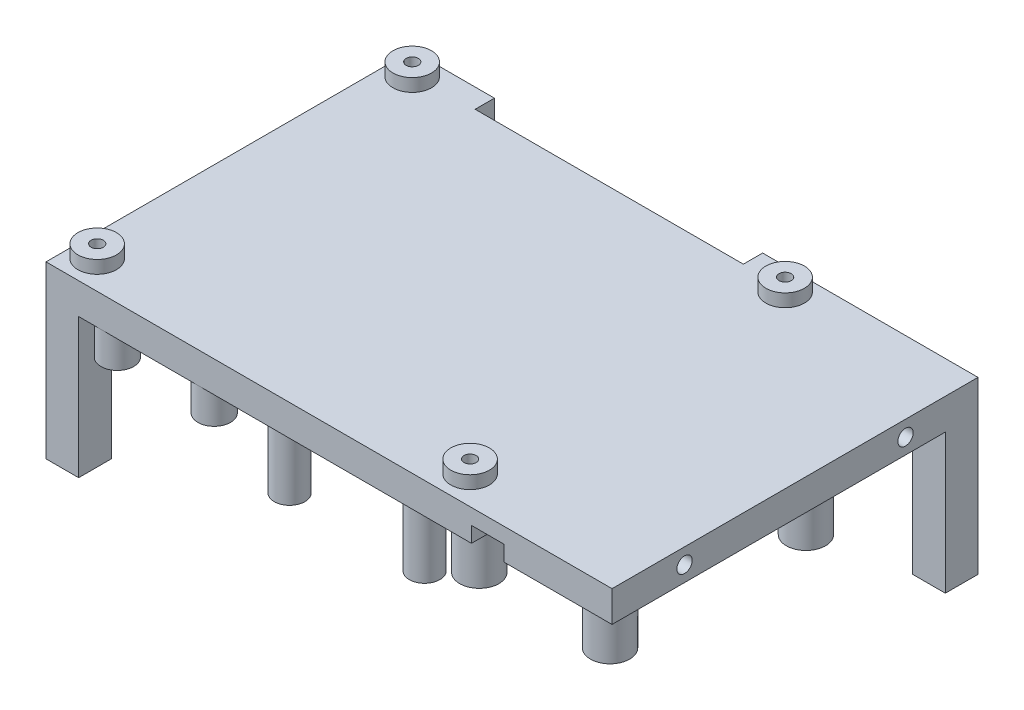
SolidWorks part; units mm, degrees
ref_plane "Front Plane" through (0, 0, 0) normal (0, 0, 1) x (1, 0, 0)
ref_plane "Top Plane" through (0, 0, 0) normal (0, 1, 0) x (1, 0, 0)
ref_plane "Right Plane" through (0, 0, 0) normal (1, 0, 0) x (0, 0, -1)
sketch "Sketch2" plane through (0, 0, 0) normal (0, 1, 0) x (1, 0, 0)
  line L1 (0, 0) -> (83.674, 0)
  line L2 (0, 0) -> (0, 58.032)
  line L3 (0, 58.032) -> (83.674, 58.032)
  line L4 (83.674, 0) -> (83.674, 58.032)
extrude "Boss-Extrude1" add sketch "Sketch2" along normal blind 2.54
sketch "Sketch4" plane through (0, 2.54, 0) normal (0, 1, 0) x (1, 0, 0)
  line L0 (88.037, 54.5711) -> (88.037, 58.032)
  line L1 (87.642, 54.5711) -> (88.432, 54.5711) construction
  line L2 (88.037, 58.032) -> (83.674, 58.032)
  line L3 (83.674, 58.032) -> (83.674, 0)
  line L4 (83.674, 0) -> (87.642, 0)
  line L5 (88.037, 54.5711) -> (88.037, 0)
  line L6 (88.037, 0) -> (87.642, 0)
extrude "Boss-Extrude2" add sketch "Sketch4" against normal blind 2.54
sketch "Sketch5" plane through (0, 2.54, 0) normal (0, 1, 0) x (1, 0, 0)
  line L0 (3.042, 56.9211) -> (0, 56.9211) construction
  line L1 (0, 58.032) -> (0, 0) construction
  line L3 (0, 56.9211) -> (88.037, 56.9211)
  line L4 (0, 56.9211) -> (0, 58.032)
  line L5 (0, 58.032) -> (88.037, 58.032)
  line L6 (88.037, 56.9211) -> (88.037, 58.032)
extrude "Cut-Extrude1" cut sketch "Sketch5" against normal blind 2.54
sketch "Sketch6" plane through (0, 2.54, 0) normal (0, 1, 0) x (1, 0, 0)
  circle A0 centre (3.542, 53.4211) radius 1.3
  circle A1 centre (3.542, 53.4211) radius 3
  circle A2 centre (61.542, 53.4211) radius 1.35
  circle A3 centre (61.542, 53.4211) radius 3
  circle A4 centre (61.542, 4.4211) radius 1.35
  circle A5 centre (61.542, 4.4211) radius 3
  circle A6 centre (3.542, 4.4211) radius 1.35
  circle A7 centre (3.542, 4.4211) radius 3
extrude "Boss-Extrude3" add sketch "Sketch6" along normal blind 3.81
sketch "Sketch7" plane through (0, 0, 0) normal (0, -1, 0) x (1, 0, 0)
  circle A0 centre (27.0717, -5.4061) radius 1.25
  circle A1 centre (27.0717, -5.4061) radius 2.55
  circle A2 centre (27.0717, -18.1061) radius 1.25
  circle A3 centre (27.0717, -18.1061) radius 2.55
  circle A4 centre (26.076, -32.9835) radius 1.4324
  circle A5 centre (26.076, -32.9835) radius 2.5467
  circle A6 centre (26.0531, -48.0443) radius 1.5084
  circle A7 centre (26.0531, -48.0443) radius 2.659
  circle A8 centre (34.2431, -29.5473) radius 1.1
  circle A9 centre (34.2431, -29.5473) radius 2.375
  circle A10 centre (55.2431, -29.5473) radius 1.1
  circle A11 centre (55.2431, -29.5473) radius 2.375
  circle A12 centre (55.2431, -42.0473) radius 1.1
  circle A13 centre (55.2431, -42.0473) radius 2.375
  circle A14 centre (34.2431, -42.0473) radius 1.1
  circle A15 centre (34.2431, -42.0473) radius 2.375
  circle A16 centre (61.9524, -36.3134) radius 1.6
  circle A17 centre (61.9524, -36.3134) radius 2.5
  circle A18 centre (82.2924, -36.3134) radius 1.6
  circle A19 centre (82.2924, -36.3134) radius 2.5
  circle A20 centre (61.9916, -5.8135) radius 1.6
  circle A21 centre (61.9916, -5.8135) radius 2.6109
  circle A22 centre (82.3316, -5.8135) radius 1.6
  circle A23 centre (82.3316, -5.8135) radius 2.6
extrude "Boss-Extrude4" add sketch "Sketch7" along normal blind 5.08
sketch "Sketch12" plane through (0, 2.54, 0) normal (0, 1, 0) x (1, 0, 0)
  line L0 (3.542, 54.7211) -> (2.242, 54.7211) construction
  line L1 (2.242, 54.7211) -> (2.242, 53.4211) construction
  line L2 (61.542, 3.0711) -> (79.322, 3.0711) construction
  line L4 (79.322, 3.0711) -> (2.242, 3.0711)
  line L5 (79.322, 3.0711) -> (79.322, 54.7211)
  line L6 (79.322, 54.7211) -> (2.242, 54.7211)
  line L7 (2.242, 3.0711) -> (2.242, 54.7211)
  line L8 (0, 56.9211) -> (88.037, 56.9211)
  line L9 (0, 56.9211) -> (0, 0)
  line L10 (0, 0) -> (88.037, 0)
  line L11 (88.037, 56.9211) -> (88.037, 0)
  circle A0 centre (3.542, 53.4211) radius 1.3 construction
  circle A1 centre (61.542, 4.4211) radius 1.35 construction
extrude "Boss-Extrude5" add sketch "Sketch12" along normal blind 2.286
sketch "Sketch13" plane through (0, 0, 0) normal (0, 0, 1) x (1, 0, 0)
  line L0 (0, 2.413) -> (5.08, 2.413) construction
  line L1 (0, 4.826) -> (0, 0) construction
  line L2 (88.037, 2.413) -> (82.957, 2.413) construction
  line L3 (88.037, 0) -> (88.037, 4.826) construction
  circle A0 centre (82.957, 2.413) radius 1.27
  circle A1 centre (5.08, 2.413) radius 1.27
extrude "Boss-Extrude6" add sketch "Sketch13" along normal blind 10.16
sketch "Sketch14" plane through (0, 0, 0) normal (0, 0, 1) x (1, 0, 0)
  circle A0 centre (5.08, 2.413) radius 1.27
  circle A1 centre (82.957, 2.413) radius 1.27
extrude "Boss-Extrude7" add sketch "Sketch14" against normal blind 10.16 from surface starting at face at (44.0185, 2.413, -56.9211)
sketch "Sketch15" plane through (0, 0, 10.16) normal (0, 0, 1) x (1, 0, 0)
  circle A0 centre (5.08, 2.413) radius 1.27
  circle A1 centre (82.957, 2.413) radius 1.27
extrude "Cut-Extrude3" cut sketch "Sketch15" against normal blind 12.7
sketch "Sketch16" plane through (0, 0, -67.0811) normal (0, 0, -1) x (-1, 0, 0)
  line L0 (-81.687, 2.413) -> (-76.607, 2.413) construction
  line L1 (-6.35, 2.413) -> (-11.43, 2.413) construction
  circle A0 centre (-82.957, 2.413) radius 1.27 construction
  circle A1 centre (-5.08, 2.413) radius 1.27 construction
  circle A2 centre (-76.607, 2.413) radius 1.27
  circle A3 centre (-11.43, 2.413) radius 1.27
extrude "Boss-Extrude8" add sketch "Sketch16" against normal blind 12.7
sketch "Sketch17" plane through (0, 0, -67.0811) normal (0, 0, -1) x (-1, 0, 0)
  circle A0 centre (-82.957, 2.413) radius 1.27
  circle A1 centre (-5.08, 2.413) radius 1.27
extrude "Cut-Extrude4" cut sketch "Sketch17" against normal up to surface (10.16 mm away) up to face at (12.7, 2.413, -56.9211)
sketch "Sketch18" plane through (0, 0, -67.0811) normal (0, 0, -1) x (-1, 0, 0)
  circle A0 centre (-76.607, 2.413) radius 1.27
  circle A1 centre (-11.43, 2.413) radius 1.27
extrude "Cut-Extrude5" cut sketch "Sketch18" against normal blind 15.24 and the other way through all
sketch "Sketch19" plane through (0, 0, 0) normal (0, -1, 0) x (1, 0, 0)
  line L1 (0, 0) -> (88.037, 0)
  line L2 (0, 0) -> (0, -56.9211)
  line L3 (0, -56.9211) -> (88.037, -56.9211)
  line L4 (88.037, 0) -> (88.037, -56.9211)
extrude "Boss-Extrude9" add sketch "Sketch19" against normal up to surface (4.826 mm away) up to face at (41.6109, 4.826, -28.9106)
sketch "Sketch20" plane through (0, 0, 0) normal (0, 0, 1) x (1, 0, 0)
  line L0 (6.542, 5) -> (6.542, 0) construction
  line L1 (6.542, 4.826) -> (6.542, 6.35) construction
  line L2 (12.722, 5) -> (1.642, 5) construction
  line L3 (0, 0) -> (88.037, 0) construction
  line L4 (6.542, 2.5) -> (9.082, 2.5) construction
  line L5 (79.7316, -0.6431) -> (79.7316, 4.1697) construction
  line L6 (79.7316, 0) -> (79.7316, -5.08) construction
  line L7 (79.7316, -0.6431) -> (79.7316, 4.826) construction
  line L8 (0, 4.826) -> (88.037, 4.826) construction
  line L9 (88.037, 2.413) -> (79.7316, 2.413) construction
  line L10 (88.037, 0) -> (88.037, 4.826) construction
  line L11 (79.7316, 2.413) -> (77.1916, 2.413) construction
  circle A0 centre (9.082, 2.5) radius 1.27
  circle A1 centre (77.1916, 2.413) radius 1.27
extrude "Cut-Extrude6" cut sketch "Sketch20" against normal blind 60.96
sketch "Sketch21" plane through (0, 0, -56.9211) normal (0, 0, -1) x (-1, 0, 0)
  circle A0 centre (-77.1916, 2.413) radius 1.27
  circle A1 centre (-9.082, 2.5) radius 1.27
extrude "Boss-Extrude10" add sketch "Sketch21" against normal blind 49.53 from offset 3.81 offset against normal yes
sketch "Sketch22" plane through (0, 0, 0) normal (0, -1, 0) x (1, 0, 0)
  line L0 (0, 0) -> (2.54, 0) construction
  line L1 (0, 0) -> (88.037, 0) construction
  line L2 (2.54, 0) -> (2.54, -2.54) construction
  line L3 (88.037, -56.9211) -> (85.497, -56.9211) construction
  line L4 (0, -56.9211) -> (88.037, -56.9211) construction
  line L5 (85.497, -56.9211) -> (85.497, -54.3811) construction
  line L6 (2.54, -2.54) -> (5.08, -2.54) construction
  line L7 (5.08, -2.54) -> (5.08, -5.08) construction
  line L8 (85.497, -54.3811) -> (82.957, -54.3811) construction
  line L9 (5.08, -5.08) -> (0, -5.08)
  line L10 (5.08, -5.08) -> (5.08, 0)
  line L11 (5.08, 0) -> (0, 0)
  line L12 (0, -5.08) -> (0, 0)
  line L13 (82.957, -54.3811) -> (82.957, -51.8411) construction
  line L14 (0, -28.4606) -> (14.3355, -28.4606) construction
  line L15 (82.957, -51.8411) -> (88.037, -51.8411)
  line L16 (82.957, -51.8411) -> (82.957, -56.9211)
  line L17 (82.957, -56.9211) -> (88.037, -56.9211)
  line L18 (88.037, -51.8411) -> (88.037, -56.9211)
  line L19 (0, -56.9211) -> (0, 0) construction
  line L20 (5.08, -56.9211) -> (0, -56.9211)
  line L21 (0, -51.8411) -> (0, -56.9211)
  line L22 (5.08, -51.8411) -> (0, -51.8411)
  line L23 (5.08, -51.8411) -> (5.08, -56.9211)
  circle A1 centre (2.54, -2.54) radius 1.27
  circle A2 centre (85.497, -54.3811) radius 1.27
  circle A3 centre (2.54, -54.3811) radius 1.27
extrude "Boss-Extrude11" add sketch "Sketch22" along normal blind 5.08 contours L20 L21 L22 L23 | A3 | L10 L9 L12 L11 | A1 | L16 L15 L18 L17 | A2
sketch "Sketch23" plane through (0, -5.08, 0) normal (0, -1, 0) x (1, 0, 0)
  line L1 (88.037, -56.9211) -> (82.957, -56.9211)
  line L2 (88.037, -56.9211) -> (88.037, -51.8411)
  line L3 (88.037, -51.8411) -> (82.957, -51.8411)
  line L4 (82.957, -56.9211) -> (82.957, -51.8411)
  line L5 (0, -56.9211) -> (5.08, -56.9211)
  line L6 (0, -56.9211) -> (0, -51.8411)
  line L7 (0, -51.8411) -> (5.08, -51.8411)
  line L8 (5.08, -56.9211) -> (5.08, -51.8411)
  line L9 (0, 0) -> (5.08, 0)
  line L10 (0, 0) -> (0, -5.08)
  line L11 (0, -5.08) -> (5.08, -5.08)
  line L12 (5.08, 0) -> (5.08, -5.08)
  circle A0 centre (2.54, -2.54) radius 1.27
  circle A1 centre (2.54, -54.3811) radius 1.27
  circle A2 centre (85.497, -54.3811) radius 1.27
extrude "Boss-Extrude12" add sketch "Sketch23" along normal blind 5.08
sketch "Sketch24" plane through (0, 0, 0) normal (0, -1, 0) x (1, 0, 0)
  line L1 (58.0196, -2.0522) -> (87.0405, -2.0522)
  line L2 (58.0196, -2.0522) -> (58.0196, -39.3757)
  line L3 (58.0196, -39.3757) -> (87.0405, -39.3757)
  line L4 (87.0405, -2.0522) -> (87.0405, -39.3757)
extrude "Cut-Extrude7" cut sketch "Sketch24" along normal blind 7.62
sketch "Sketch25" plane through (0, 0, 0) normal (0, -1, 0) x (1, 0, 0)
  circle A0 centre (64.5432, -22.4957) radius 2.5083
  circle A1 centre (64.5432, -22.4957) radius 3.5101
  circle A2 centre (80.977, -22.4957) radius 2.5082
  circle A3 centre (80.977, -22.4957) radius 3.7782
extrude "Boss-Extrude13" add sketch "Sketch25" along normal blind 3.81
sketch "Sketch26" plane through (0, 0, 0) normal (0, -1, 0) x (1, 0, 0)
  circle A0 centre (64.5432, -22.4957) radius 2.5083
  circle A2 centre (80.977, -22.4957) radius 2.5082
extrude "Cut-Extrude8" cut sketch "Sketch26" against normal blind 2.54
sketch "Sketch27" plane through (0, -3.81, 0) normal (0, -1, 0) x (1, 0, 0)
  circle A0 centre (80.977, -22.4957) radius 4.3247
  circle A1 centre (64.5432, -22.4957) radius 6.369
extrude "Cut-Extrude9" cut sketch "Sketch27" against normal up to surface (3.81 mm away) up to face at (80.977, 0, -26.274)
sketch "Sketch28" plane through (0, 0, 0) normal (0, -1, 0) x (1, 0, 0)
  circle A0 centre (64.5432, -22.4957) radius 2.5083
  circle A1 centre (80.977, -22.4957) radius 2.5082
extrude "Boss-Extrude14" add sketch "Sketch28" against normal up to surface (4.826 mm away) contours A0 | A1 up to face at (3.542, 4.826, -1.4211)
sketch "Sketch29" plane through (0, 0, 0) normal (0, -1, 0) x (1, 0, 0)
  circle A0 centre (83.3807, -34.8151) radius 1.6
  circle A2 centre (63.08, -4.3152) radius 1.6
  circle A4 centre (83.42, -4.3152) radius 1.6
  circle A7 centre (83.42, -4.3152) radius 3.048
  circle A8 centre (63.08, -4.3152) radius 3.048
  circle A9 centre (63.0407, -34.8151) radius 1.6
  circle A10 centre (63.0407, -34.8151) radius 3.048
  circle A11 centre (83.3807, -34.8151) radius 3.048
extrude "Boss-Extrude15" add sketch "Sketch29" along normal blind 7.62
sketch "Sketch30" plane through (0, -10.16, 0) normal (0, -1, 0) x (1, 0, 0)
  line L1 (0, 0) -> (5.08, 0)
  line L2 (0, 0) -> (0, -5.08)
  line L3 (0, -5.08) -> (5.08, -5.08)
  line L4 (5.08, 0) -> (5.08, -5.08)
  line L5 (0, -51.8411) -> (5.08, -51.8411)
  line L6 (0, -51.8411) -> (0, -56.9211)
  line L7 (0, -56.9211) -> (5.08, -56.9211)
  line L8 (5.08, -51.8411) -> (5.08, -56.9211)
  line L9 (82.957, -51.8411) -> (88.037, -51.8411)
  line L10 (82.957, -51.8411) -> (82.957, -56.9211)
  line L11 (82.957, -56.9211) -> (88.037, -56.9211)
  line L12 (88.037, -51.8411) -> (88.037, -56.9211)
  circle A0 centre (2.54, -2.54) radius 1.27
  circle A1 centre (2.54, -54.3811) radius 1.27
  circle A2 centre (85.497, -54.3811) radius 1.27
extrude "Boss-Extrude16" add sketch "Sketch30" along normal blind 5.08
sketch "Sketch32" plane through (0, 0, -56.9211) normal (0, 0, -1) x (-1, 0, 0)
  line L0 (-5.08, -15.24) -> (-5.08, 0) construction
  line L1 (0, -15.24) -> (-5.08, -15.24)
  line L2 (0, -15.24) -> (0, -12.7127)
  line L3 (0, -12.7127) -> (-5.08, -12.7127)
  line L4 (-5.08, -15.24) -> (-5.08, -12.7127)
  line L5 (1.259, -12.7127) -> (-6.3609, -12.7127) construction
  line L6 (-88.037, -15.24) -> (-88.037, 4.826) construction
  line L7 (-82.957, -15.24) -> (-88.037, -15.24)
  line L8 (-82.957, -15.24) -> (-82.957, -12.7127)
  line L9 (-82.957, -12.7127) -> (-88.037, -12.7127)
  line L10 (-88.037, -15.24) -> (-88.037, -12.7127)
  line L11 (-81.8431, -12.7127) -> (-89.463, -12.7127) construction
extrude "Cut-Extrude10" cut sketch "Sketch32" against normal up to surface (56.9211 mm away) up to face at (10.352, 2.5, 0)
sketch "Sketch34" plane through (0, 0, -56.9211) normal (0, 0, -1) x (-1, 0, 0)
  circle A0 centre (-77.1916, 2.413) radius 1.2
  circle A1 centre (-77.1916, 2.413) radius 1.27
  circle A2 centre (-9.082, 2.5) radius 1.2
  circle A3 centre (-9.082, 2.5) radius 1.27
extrude "Boss-Extrude17" add sketch "Sketch34" against normal blind 10
sketch "Sketch35" plane through (0, 0, 0) normal (0, 0, 1) x (1, 0, 0)
  circle A0 centre (9.082, 2.5) radius 1.2
  circle A1 centre (9.082, 2.5) radius 1.27
  circle A2 centre (77.1916, 2.413) radius 1.2
  circle A3 centre (77.1916, 2.413) radius 1.27
extrude "Boss-Extrude18" add sketch "Sketch35" against normal blind 10
sketch "Sketch36" plane through (0, 4.826, 0) normal (0, 1, 0) x (1, 0, 0)
  circle A0 centre (3.542, 53.4211) radius 0.95
  circle A1 centre (3.542, 53.4211) radius 3
  circle A2 centre (61.542, 53.4211) radius 0.95
  circle A3 centre (61.542, 53.4211) radius 3
  circle A4 centre (61.542, 4.4211) radius 0.95
  circle A5 centre (61.542, 4.4211) radius 3
  circle A6 centre (3.542, 4.4211) radius 0.95
  circle A7 centre (3.542, 4.4211) radius 3
extrude "Boss-Extrude19" add sketch "Sketch36" along normal blind 2
sketch "Sketch37" plane through (0, 4.826, 0) normal (0, 1, 0) x (1, 0, 0)
  circle A0 centre (3.542, 53.4211) radius 0.95
  circle A1 centre (61.542, 53.4211) radius 0.95
  circle A2 centre (61.542, 4.4211) radius 0.95
  circle A3 centre (3.542, 4.4211) radius 0.95
extrude "Cut-Extrude11" cut sketch "Sketch37" against normal blind 2
sketch "Sketch38" plane through (0, 0, 0) normal (0, -1, 0) x (1, 0, 0)
  line L0 (55.2431, -43.1473) -> (55.2431, -40.9473) construction
  line L3 (26.0531, -49.5527) -> (26.0531, -46.5359) construction
  line L4 (27.0717, -19.3561) -> (27.0717, -16.8561) construction
  circle A0 centre (55.2431, -42.0473) radius 1.1 construction
  circle A1 centre (55.2431, -42.0473) radius 1.1 construction
  circle A6 centre (26.0531, -48.0443) radius 1.5084 construction
  circle A7 centre (26.0531, -48.0443) radius 1.5084 construction
  circle A8 centre (27.0717, -18.1061) radius 1.25 construction
  circle A9 centre (27.0717, -18.1061) radius 1.25 construction
  circle A24 centre (26.0531, -48.0443) radius 1.2
  circle A25 centre (26.0531, -48.0443) radius 1.5084
  circle A26 centre (26.076, -32.9835) radius 1.2
  circle A27 centre (26.076, -32.9835) radius 1.4324
  circle A28 centre (27.0717, -18.1061) radius 1.2
  circle A29 centre (27.0717, -18.1061) radius 1.25
  circle A30 centre (27.0717, -5.4061) radius 1.2
  circle A31 centre (27.0717, -5.4061) radius 1.25
  circle A32 centre (55.2431, -42.0473) radius 0.95
  circle A33 centre (55.2431, -42.0473) radius 1.1
  circle A34 centre (55.2431, -29.5473) radius 0.95
  circle A35 centre (55.2431, -29.5473) radius 1.1
  circle A36 centre (34.2431, -29.5473) radius 0.95
  circle A37 centre (34.2431, -29.5473) radius 1.1
  circle A38 centre (34.2431, -42.0473) radius 0.95
  circle A39 centre (34.2431, -42.0473) radius 1.1
extrude "Boss-Extrude20" add sketch "Sketch38" along normal up to surface (5.08 mm away) up to face at (26.0531, -5.08, -50.7033)
sketch "Sketch39" plane through (0, 0, 0) normal (0, -1, 0) x (1, 0, 0)
  circle A0 centre (63.08, -4.3152) radius 1.2
  circle A1 centre (63.08, -4.3152) radius 1.6
  circle A2 centre (83.42, -4.3152) radius 1.2
  circle A3 centre (83.42, -4.3152) radius 1.6
  circle A4 centre (63.0407, -34.8151) radius 1.2
  circle A5 centre (63.0407, -34.8151) radius 1.6
  circle A6 centre (83.3807, -34.8151) radius 1.2
  circle A7 centre (83.3807, -34.8151) radius 1.6
extrude "Boss-Extrude21" add sketch "Sketch39" along normal up to surface (7.62 mm away) up to face at (63.08, -7.62, -7.3632)
sketch "Sketch40" plane through (0, 0, 0) normal (0, -1, 0) x (1, 0, 0)
  circle A0 centre (2.54, -2.54) radius 1.2
  circle A1 centre (2.54, -2.54) radius 1.27
  circle A2 centre (2.54, -54.3811) radius 1.2
  circle A3 centre (2.54, -54.3811) radius 1.27
  circle A4 centre (85.497, -54.3811) radius 1.2
  circle A5 centre (85.497, -54.3811) radius 1.27
extrude "Boss-Extrude22" add sketch "Sketch40" along normal up to surface (12.7127 mm away) up to face at (2.54, -12.7127, -53.1111)
sketch "Sketch41" plane through (0, 0, 0) normal (0, -1, 0) x (1, 0, 0)
  line L0 (34.2431, -29.5473) -> (55.2431, -29.5473) construction
  line L1 (34.2431, -29.5473) -> (34.2431, -42.0473) construction
  line L2 (34.2431, -17.0473) -> (34.2431, -29.5473) construction
  circle A4 centre (34.2431, -17.0473) radius 2.375
  circle A5 centre (34.2431, -17.0473) radius 0.95
  circle A6 centre (55.2431, -17.0473) radius 0.95
  circle A7 centre (55.2431, -17.0473) radius 2.375
extrude "Boss-Extrude23" add sketch "Sketch41" along normal blind 2
sketch "Sketch42" plane through (0, 0, 0) normal (0, -1, 0) x (1, 0, 0)
  circle A0 centre (34.2431, -42.0473) radius 3.5191
  circle A1 centre (55.2431, -42.0473) radius 3.8156
extrude "Cut-Extrude12" cut sketch "Sketch42" along normal blind 10
sketch "Sketch43" plane through (0, 0, 0) normal (0, -1, 0) x (1, 0, 0)
  circle A0 centre (34.2431, -17.0473) radius 0.95
  circle A1 centre (34.2431, -17.0473) radius 2.375
  circle A2 centre (55.2431, -17.0473) radius 0.95
  circle A3 centre (55.2431, -17.0473) radius 2.375
extrude "Boss-Extrude24" add sketch "Sketch43" along normal up to surface (5.08 mm away) up to face at (34.2431, -5.08, -31.9223)
sketch "Sketch44" plane through (0, 4.826, 0) normal (0, 1, 0) x (1, 0, 0)
  line L0 (6.542, 53.4211) -> (10.542, 53.4211) construction
  line L1 (58.542, 53.4211) -> (54.542, 53.4211) construction
  line L2 (54.542, 53.4211) -> (54.542, 56.9211) construction
  line L3 (88.037, 56.9211) -> (0, 56.9211) construction
  line L5 (54.542, 56.9211) -> (10.542, 56.9211)
  line L6 (54.542, 56.9211) -> (54.542, 53.9211)
  line L7 (54.542, 53.9211) -> (10.542, 53.9211)
  line L8 (10.542, 56.9211) -> (10.542, 53.9211)
  circle A0 centre (3.542, 53.4211) radius 3 construction
  circle A1 centre (3.542, 53.4211) radius 3 construction
  circle A2 centre (61.542, 53.4211) radius 3 construction
  circle A3 centre (61.542, 53.4211) radius 3 construction
extrude "Cut-Extrude13" cut sketch "Sketch44" against normal blind 10
sketch "Sketch45" plane through (0, 0, 0) normal (0, -1, 0) x (1, 0, 0)
  circle A2 centre (34.2215, -35.9267) radius 1.2
  circle A3 centre (34.2215, -35.9267) radius 2.55
  circle A4 centre (34.2215, -48.6267) radius 1.2
  circle A5 centre (34.2215, -48.6267) radius 2.55
extrude "Boss-Extrude25" add sketch "Sketch45" along normal blind 8.5
sketch "Sketch46" plane through (0, 0, 0) normal (0, -1, 0) x (1, 0, 0)
  circle A0 centre (27.0717, -5.4061) radius 3.087
  circle A1 centre (27.0717, -18.1061) radius 3.4948
extrude "Cut-Extrude14" cut sketch "Sketch46" along normal up to surface (5.08 mm away) up to face at (27.0717, -5.08, -7.9561)
sketch "Sketch47" plane through (0, 0, 0) normal (0, -1, 0) x (1, 0, 0)
  circle A10 centre (34.2431, -17.0473) radius 2.375
  circle A11 centre (55.2431, -17.0473) radius 2.375
  circle A12 centre (55.2431, -29.5473) radius 2.375
extrude "Cut-Extrude15" cut sketch "Sketch47" along normal up to surface (5.08 mm away) up to face at (55.2431, -5.08, -17.9973)
sketch "Sketch48" plane through (0, 0, 0) normal (0, -1, 0) x (1, 0, 0)
  circle A2 centre (34.1591, -3.7219) radius 0.95
  circle A3 centre (34.1591, -3.7219) radius 2.375
  circle A4 centre (34.1591, -16.2219) radius 0.95
  circle A5 centre (34.1591, -16.2219) radius 2.375
  circle A6 centre (55.1591, -16.2219) radius 0.95
  circle A7 centre (55.1591, -16.2219) radius 2.375
  circle A8 centre (55.1591, -3.7219) radius 0.95
  circle A9 centre (55.1591, -3.7219) radius 2.375
extrude "Boss-Extrude26" add sketch "Sketch48" along normal up to surface (5.08 mm away) up to face at (34.2431, -5.08, -31.9223)
sketch "Sketch49" plane through (0, 0, 0) normal (0, -1, 0) x (1, 0, 0)
  circle A0 centre (34.2431, -29.5473) radius 2.375
extrude "Cut-Extrude16" cut sketch "Sketch49" along normal up to surface (5.08 mm away) up to face at (34.2431, -5.08, -31.9223)
sketch "Sketch51" plane through (0, 0, 0) normal (0, -1, 0) x (1, 0, 0)
  circle A0 centre (8.5571, -6.3787) radius 1.2
  circle A1 centre (8.5571, -6.3787) radius 2.5467
  circle A2 centre (23.6179, -6.4015) radius 1.2
  circle A3 centre (23.6179, -6.4015) radius 2.5467
extrude "Boss-Extrude27" add sketch "Sketch51" along normal blind 4
sketch "Sketch52" plane through (0, 0, 0) normal (0, -1, 0) x (1, 0, 0)
  line L1 (30.0179, -28.9808) -> (17.6255, -28.9808)
  line L2 (30.0179, -28.9808) -> (30.0179, -52.4413)
  line L3 (30.0179, -52.4413) -> (17.6255, -52.4413)
  line L4 (17.6255, -28.9808) -> (17.6255, -52.4413)
extrude "Cut-Extrude17" cut sketch "Sketch52" along normal up to surface (5.08 mm away) up to face at (26.0531, -5.08, -50.7033)
sketch "Sketch53" plane through (0, 0, 0) normal (0, 0, 1) x (1, 0, 0)
  line L0 (66.1782, 0) -> (66.1782, 4.826) construction
  line L1 (5.08, 0) -> (88.037, 0) construction
  line L2 (0, 4.826) -> (88.037, 4.826) construction
  line L3 (66.1782, 2.413) -> (71.2582, 2.413) construction
  line L4 (71.2582, 2.413) -> (71.2582, 0) construction
  line L5 (71.2582, 2.413) -> (71.2582, 0)
  line L10 (71.2582, 0) -> (66.1782, 0)
  line L11 (66.1782, 0) -> (66.1782, 2.413)
  line L12 (66.1782, 2.413) -> (71.2582, 2.413)
revolve "Cut-Revolve1" cut sketch "Sketch53" angle 96 about L10
fillet "Fillet1" radius 20 1 edges at (68.7182, 0, -2.413)
sketch "Sketch54" plane through (0, 0, -53.9211) normal (0, 0, -1) x (-1, 0, 0)
  line L0 (-10.282, 2.5) -> (-12.822, 2.5) construction
  line L1 (-10.542, 4.826) -> (-54.542, 4.826) construction
  line L2 (-12.822, 4.826) -> (-10.542, 4.826)
  line L3 (-12.822, 4.826) -> (-12.822, 0)
  line L4 (-12.822, 0) -> (-10.542, 0)
  line L5 (-10.542, 4.826) -> (-10.542, 0)
  circle A0 centre (-9.082, 2.5) radius 1.2 construction
extrude "Boss-Extrude28" add sketch "Sketch54" along normal up to surface (3 mm away) up to face at (5.2073, -2.6289, -56.9211)
sketch "Sketch55" plane through (0, 0, 0) normal (0, -1, 0) x (1, 0, 0)
  line L1 (34.2215, -53.9211) -> (34.2215, -51.3711) construction
  line L2 (54.542, -53.9211) -> (12.822, -53.9211) construction
  line L3 (34.2215, -51.3711) -> (34.2215, -38.6711) construction
  circle A1 centre (34.2215, -51.3711) radius 2.55
  circle A2 centre (34.2215, -51.3711) radius 1.2
  circle A4 centre (34.2215, -38.6711) radius 1.2
  circle A5 centre (34.2215, -38.6711) radius 2.55
extrude "Boss-Extrude29" add sketch "Sketch55" along normal blind 4
sketch "Sketch56" plane through (0, -8.5, 0) normal (0, -1, 0) x (1, 0, 0)
  circle A0 centre (34.2215, -35.9267) radius 2.55
  circle A1 centre (34.2215, -48.6267) radius 2.55
extrude "Cut-Extrude18" cut sketch "Sketch56" against normal up to surface (8.5 mm away) up to face at (2.54, 0, -55.5811)
sketch "Sketch57" plane through (0, 0, 0) normal (0, -1, 0) x (1, 0, 0)
  circle A0 centre (34.2215, -51.3711) radius 1.2
  circle A1 centre (34.2215, -51.3711) radius 2.55
  circle A2 centre (34.2215, -38.6711) radius 1.2
  circle A3 centre (34.2215, -38.6711) radius 2.55
extrude "Boss-Extrude30" add sketch "Sketch57" along normal blind 8.5
sketch "Sketch58" plane through (0, 0, 0) normal (0, -1, 0) x (1, 0, 0)
  line L0 (16.0875, -2.5467) -> (16.0875, 1.8828) construction
  line L1 (8.5571, 0) -> (8.5571, -2.5467) construction
  line L2 (5.08, 0) -> (66.1782, 0) construction
  line L3 (8.5571, -2.5467) -> (23.618, -2.5467) construction
  circle A2 centre (8.5571, -2.5467) radius 1.2
  circle A3 centre (8.5571, -2.5467) radius 2.5467
  circle A4 centre (23.618, -2.5467) radius 1.2
  circle A5 centre (23.618, -2.5467) radius 2.5467
extrude "Boss-Extrude31" add sketch "Sketch58" along normal blind 2
sketch "Sketch59" plane through (0, 0, 0) normal (0, -1, 0) x (1, 0, 0)
  circle A0 centre (8.5571, -6.3787) radius 2.5467
  circle A1 centre (23.6179, -6.4015) radius 2.5467
extrude "Cut-Extrude19" cut sketch "Sketch59" along normal up to surface (4 mm away) up to face at (8.5571, -4, -8.9255)
sketch "Sketch60" plane through (0, 0, 0) normal (0, -1, 0) x (1, 0, 0)
  circle A1 centre (23.618, -2.5467) radius 1.2
  circle A2 centre (23.618, -2.5467) radius 2.5467
  circle A4 centre (8.5571, -2.5467) radius 1.2
  circle A5 centre (8.5571, -2.5467) radius 2.5467
extrude "Boss-Extrude32" add sketch "Sketch60" along normal blind 4
sketch "Sketch61" plane through (0, -12.7127, 0) normal (0, -1, 0) x (1, 0, 0)
  line L1 (5.08, -56.9211) -> (0, -56.9211)
  line L2 (5.08, -56.9211) -> (5.08, -51.8411)
  line L3 (5.08, -51.8411) -> (0, -51.8411)
  line L4 (0, -56.9211) -> (0, -51.8411)
  line L5 (5.08, 0) -> (0, 0)
  line L6 (5.08, 0) -> (5.08, -5.08)
  line L7 (5.08, -5.08) -> (0, -5.08)
  line L8 (0, 0) -> (0, -5.08)
  line L9 (82.957, -56.9211) -> (88.037, -56.9211)
  line L10 (82.957, -56.9211) -> (82.957, -51.8411)
  line L11 (82.957, -51.8411) -> (88.037, -51.8411)
  line L12 (88.037, -56.9211) -> (88.037, -51.8411)
  circle A0 centre (2.54, -54.3811) radius 1.2
  circle A1 centre (2.54, -2.54) radius 1.2
  circle A2 centre (85.497, -54.3811) radius 1.2
extrude "Boss-Extrude34" add sketch "Sketch61" along normal blind 4.65
sketch "Sketch62" plane through (0, 0, 0) normal (0, -1, 0) x (1, 0, 0)
  circle A0 centre (34.1591, -3.7219) radius 0.95
  circle A1 centre (34.1591, -3.7219) radius 2.375
  circle A2 centre (55.1591, -3.7219) radius 0.95
  circle A3 centre (55.1591, -3.7219) radius 2.375
  circle A4 centre (34.1591, -16.2219) radius 0.95
  circle A5 centre (34.1591, -16.2219) radius 2.375
  circle A6 centre (55.1591, -16.2219) radius 0.95
  circle A7 centre (55.1591, -16.2219) radius 2.375
extrude "Boss-Extrude36" add sketch "Sketch62" along normal blind 6 from surface starting at face at (34.1591, -5.08, -4.6719)
sketch "Sketch63" plane through (0, -17.3627, 0) normal (0, -1, 0) x (1, 0, 0)
  line L1 (0, 0) -> (5.08, 0)
  line L2 (0, 0) -> (0, -5.08)
  line L3 (0, -5.08) -> (5.08, -5.08)
  line L4 (5.08, 0) -> (5.08, -5.08)
  line L5 (0, -56.9211) -> (5.08, -56.9211)
  line L6 (0, -56.9211) -> (0, -51.8411)
  line L7 (0, -51.8411) -> (5.08, -51.8411)
  line L8 (5.08, -56.9211) -> (5.08, -51.8411)
  line L9 (88.037, -56.9211) -> (82.957, -56.9211)
  line L10 (88.037, -56.9211) -> (88.037, -51.8411)
  line L11 (88.037, -51.8411) -> (82.957, -51.8411)
  line L12 (82.957, -56.9211) -> (82.957, -51.8411)
  circle A0 centre (2.54, -2.54) radius 1.2
  circle A1 centre (2.54, -54.3811) radius 1.2
  circle A2 centre (85.497, -54.3811) radius 1.2
sketch "Sketch64" plane through (0, -17.3627, 0) normal (0, -1, 0) x (1, 0, 0)
  line L1 (0, 0) -> (5.08, 0)
  line L2 (0, 0) -> (0, -5.08)
  line L3 (0, -5.08) -> (5.08, -5.08)
  line L4 (5.08, 0) -> (5.08, -5.08)
  line L5 (0, -56.9211) -> (5.08, -56.9211)
  line L6 (0, -56.9211) -> (0, -51.8411)
  line L7 (0, -51.8411) -> (5.08, -51.8411)
  line L8 (5.08, -56.9211) -> (5.08, -51.8411)
  line L9 (88.037, -56.9211) -> (82.957, -56.9211)
  line L10 (88.037, -56.9211) -> (88.037, -51.8411)
  line L11 (88.037, -51.8411) -> (82.957, -51.8411)
  line L12 (82.957, -56.9211) -> (82.957, -51.8411)
  circle A0 centre (2.54, -2.54) radius 1.2
  circle A1 centre (2.54, -54.3811) radius 1.2
  circle A2 centre (85.497, -54.3811) radius 1.2
sketch "Sketch65" plane through (0, -4, 0) normal (0, -1, 0) x (1, 0, 0)
  circle A0 centre (8.5571, -2.5467) radius 1.2
  circle A1 centre (8.5571, -2.5467) radius 2.5467
  circle A2 centre (23.618, -2.5467) radius 1.2
  circle A3 centre (23.618, -2.5467) radius 2.5467
extrude "Boss-Extrude38" add sketch "Sketch65" along normal blind 1
sketch "Sketch66" plane through (88.037, 0, 0) normal (1, 0, 0) x (0, 0, -1)
  line L0 (7.3632, 0) -> (31.7671, 0) construction
  line L1 (0, 2.413) -> (7.4211, 2.413) construction
  line L3 (0, 0) -> (0, 4.826) construction
  line L5 (7.4211, 2.413) -> (10.0348, 2.413) construction
  line L6 (10.0348, 2.413) -> (12.5174, 2.413) construction
  line L7 (12.5174, 2.413) -> (14.9689, 2.413) construction
  line L8 (28.4606, 4.826) -> (28.4606, 0) construction
  line L15 (0, 4.826) -> (56.9211, 4.826) construction
  circle A1 centre (11.2761, 2.413) radius 1.1938
  circle A2 centre (45.645, 2.413) radius 1.1938
extrude "Cut-Extrude21" cut sketch "Sketch66" against normal blind 8
sketch "Sketch68" plane through (0, 0, -56.9211) normal (0, 0, -1) x (-1, 0, 0)
  circle A0 centre (-77.1916, 2.413) radius 1.2
  circle A1 centre (-9.082, 2.5) radius 1.2
extrude "Boss-Extrude40" add sketch "Sketch68" against normal blind 8
sketch "Sketch69" plane through (0, 0, 0) normal (0, 0, 1) x (1, 0, 0)
  circle A0 centre (9.082, 2.5) radius 1.2
  circle A1 centre (77.1916, 2.413) radius 1.2
extrude "Boss-Extrude41" add sketch "Sketch69" against normal blind 8
sketch "Sketch70" plane through (88.037, 0, 0) normal (1, 0, 0) x (0, 0, -1)
  circle A0 centre (11.2761, 2.413) radius 1.1938
  circle A1 centre (45.645, 2.413) radius 1.1938
extrude "Cut-Extrude22" cut sketch "Sketch70" along normal blind 8 from surface starting at face at (0, -7.4749, -28.4606)
sketch "Sketch71" plane through (0, -17.3627, 0) normal (0, -1, 0) x (1, 0, 0)
  line L1 (5.08, -5.08) -> (0, -5.08)
  line L2 (5.08, -5.08) -> (5.08, 0)
  line L3 (5.08, 0) -> (0, 0)
  line L4 (0, -5.08) -> (0, 0)
  line L5 (0, -51.8411) -> (5.08, -51.8411)
  line L6 (0, -51.8411) -> (0, -56.9211)
  line L7 (0, -56.9211) -> (5.08, -56.9211)
  line L8 (5.08, -51.8411) -> (5.08, -56.9211)
  line L9 (82.957, -51.8411) -> (88.037, -51.8411)
  line L10 (82.957, -51.8411) -> (82.957, -56.9211)
  line L11 (82.957, -56.9211) -> (88.037, -56.9211)
  line L12 (88.037, -51.8411) -> (88.037, -56.9211)
  circle A0 centre (2.54, -2.54) radius 1.2
  circle A1 centre (2.54, -54.3811) radius 1.2
  circle A2 centre (85.497, -54.3811) radius 1.2
extrude "Boss-Extrude42" add sketch "Sketch71" along normal blind 4.35
